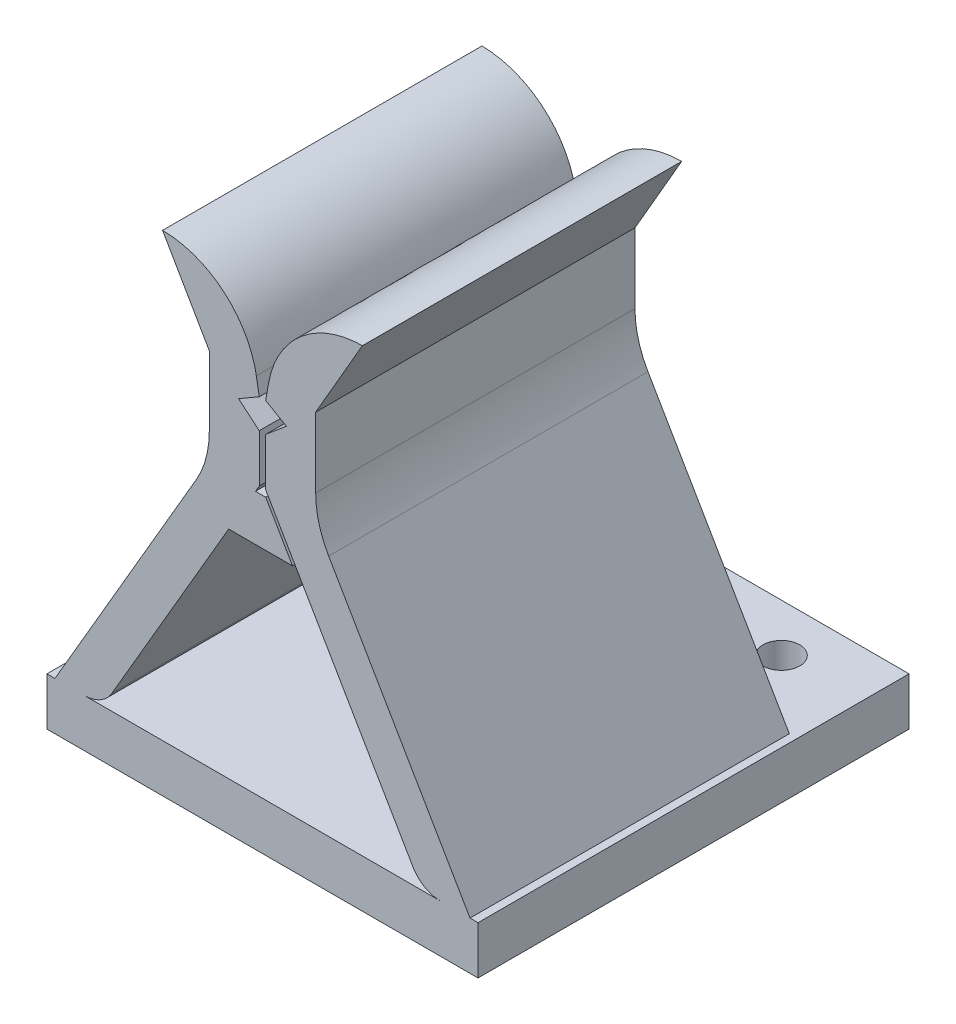
SolidWorks part; units mm, degrees
ref_plane "Piano frontale" through (0, 0, 0) normal (0, 0, 1) x (1, 0, 0)
ref_plane "Piano superiore" through (0, 0, 0) normal (0, 1, 0) x (1, 0, 0)
ref_plane "Piano destro" through (0, 0, 0) normal (1, 0, 0) x (0, 0, -1)
sketch "Schizzo1" plane through (0, 0, 0) normal (0, 0, 1) x (1, 0, 0)
  line L1 (0, 0) -> (50, 0)
  line L2 (0, 0) -> (0, 3)
  line L3 (0, 3) -> (50, 3)
  line L4 (50, 0) -> (50, 3)
  dimension "D1" = 50
  dimension "D2" = 3
extrude "Estrusione-Estrusione1" add sketch "Schizzo1" along normal blind 20
sketch "Schizzo2" plane through (0, 0, 20) normal (0, 0, 1) x (1, 0, 0)
  line L0 (25, 0) -> (25, 22.9285) construction
  line L1 (0, 0) -> (50, 0) construction
  line L2 (12, 3) -> (21.6677, 19.61)
  line L3 (50, 3) -> (0, 3) construction
  line L4 (21.6677, 19.61) -> (21.6677, 25.61)
  line L5 (21.6677, 25.61) -> (18.742, 30.6774)
  line L6 (18.742, 30.6774) -> (23.742, 30.6774)
  line L7 (12, 3) -> (15, 3)
  line L10 (23.742, 30.6774) -> (24.8, 24.6774)
  line L11 (24.8, 24.6774) -> (23.501, 23.9274)
  line L12 (23.501, 23.9274) -> (24.8, 22.8373)
  line L13 (26.499, 23.9274) -> (25.2, 22.8373)
  line L14 (25.2, 24.6774) -> (26.499, 23.9274)
  line L15 (26.258, 30.6774) -> (25.2, 24.6774)
  line L18 (38, 3) -> (35, 3)
  line L19 (31.258, 30.6774) -> (26.258, 30.6774)
  line L20 (28.3323, 25.61) -> (31.258, 30.6774)
  line L21 (28.3323, 19.61) -> (28.3323, 25.61)
  line L22 (38, 3) -> (28.3323, 19.61)
  line L23 (24.8, 22.8373) -> (24.8, 19.8373)
  line L24 (15, 3) -> (24.8, 19.8373)
  line L25 (35, 3) -> (25.2, 19.8373)
  line L26 (25.2, 22.8373) -> (25.2, 19.8373)
  dimension "D6" = 70
  dimension "D1" = 12
  dimension "D2" = 3
  dimension "D3" = 150
  dimension "D4" = 3
  dimension "D5" = 0.2
  dimension "D7" = 6
  dimension "D8" = 6
  dimension "D9" = 100
  dimension "D10" = 5
  dimension "D11" = 16.61
  dimension "D12" = 1.5
extrude "Estrusione-Estrusione2" add sketch "Schizzo2" against normal up to surface (20 mm away) separate body up to face at (25, 1.5, 0)
fillet "Raccordo2" radius 6 1 edges at (23.742, 30.6774, 10) first distance on face at (21.242, 30.6774, 10)
fillet "Raccordo3" radius 6 1 edges at (26.258, 30.6774, 10) first distance on face at (25.729, 27.6774, 10)
fillet "Raccordo4" radius 6 1 edges at (28.3323, 19.61, 10)
fillet "Raccordo5" radius 6 1 edges at (21.6677, 19.61, 10)
fillet "Raccordo7" radius 2 1 edges at (35, 3, 10)
fillet "Raccordo8" radius 2 1 edges at (15, 3, 10)
sketch "Schizzo5" plane through (0, 3, 0) normal (0, 1, 0) x (1, 0, 0)
  line L0 (50, -20) -> (0, -20) construction
  line L1 (0, 0) -> (11.5, 0)
  line L2 (0, 0) -> (0, -20)
  line L3 (0, -20) -> (11.5, -20)
  line L4 (11.5, 0) -> (11.5, -20)
  line L5 (12, 0) -> (12, -20) construction
  line L6 (25, -20) -> (25, 0) construction
  line L7 (50, 0) -> (0, 0) construction
  line L8 (38.5, 0) -> (38.5, -20)
  line L9 (50, -20) -> (38.5, -20)
  line L10 (50, 0) -> (50, -20)
  line L11 (50, 0) -> (38.5, 0)
  dimension "D1" = 0.5
extrude "Taglio-Estrusione2" cut sketch "Schizzo5" against normal up to surface (3 mm away) up to face at (25, 0, 10)
sketch "Schizzo9" plane through (0, 0, 20) normal (0, 0, 1) x (1, 0, 0)
  line L0 (24.5641, 19.432) -> (22.8843, 16.546)
  line L1 (15.5785, 3.9939) -> (24.8, 19.8373) construction
  line L2 (22.8843, 16.546) -> (26.8843, 16.546)
  line L3 (26.8843, 16.546) -> (25.2045, 19.432)
  line L4 (25.2045, 19.432) -> (24.5641, 19.432)
  line L7 (25.2, 19.8373) -> (34.4215, 3.9939) construction
  dimension "D1" = 4
  dimension "D2" = 0.2
  dimension "D3" = 0.6404
extrude "Estrusione-Estrusione7" add sketch "Schizzo9" against normal up to surface (20 mm away) up to face at (20.2418, 18.9106, 0)
sketch "Schizzo12" plane through (0, 3, 0) normal (0, 1, 0) x (1, 0, 0)
  line L0 (38.5, 0) -> (38.5, -20) construction
  line L1 (11.5, 0) -> (38.5, 0)
  line L2 (11.5, 0) -> (11.5, 7)
  line L3 (11.5, 7) -> (38.5, 7)
  line L4 (38.5, 0) -> (38.5, 7)
  circle A0 centre (16.5, 4) radius 1.15
  circle A1 centre (33.5, 4) radius 1.15
  dimension "D5" = 2.3
  dimension "D1" = 7
  dimension "D2" = 3
  dimension "D3" = 5
  dimension "D4" = 5
extrude "Estrusione-Estrusione9" add sketch "Schizzo12" against normal up to surface (3 mm away) up to face at (25, 0, 10)
